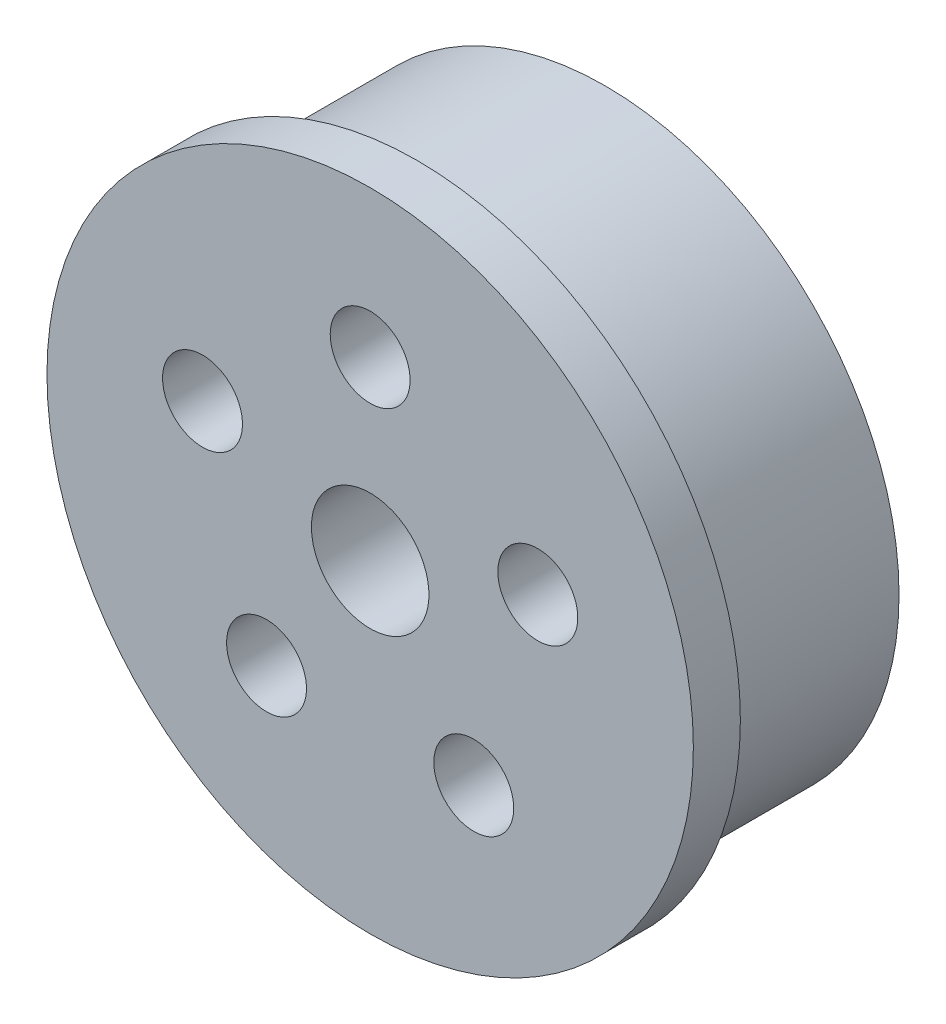
SolidWorks part; units mm, degrees
material "A2017"
ref_plane "正面" through (0, 0, 0) normal (0, 0, 1) x (1, 0, 0)
ref_plane "平面" through (0, 0, 0) normal (0, 1, 0) x (1, 0, 0)
ref_plane "右側面" through (0, 0, 0) normal (1, 0, 0) x (0, 0, -1)
sketch "ｽｹｯﾁ1" plane through (0, 0, 0) normal (0, 0, 1) x (1, 0, 0)
  circle A0 centre (0, 0) radius 12.5
  circle A1 centre (0, 7.5) radius 1.5
  circle A2 centre (0, 0) radius 7.5 construction
  circle A3 centre (7.1329, 2.3176) radius 1.5
  circle A4 centre (4.4084, -6.0676) radius 1.5
  circle A5 centre (-4.4084, -6.0676) radius 1.5
  circle A6 centre (-7.1329, 2.3176) radius 1.5
  point P16 (0, 0)
  dimension "D1" = 25
  dimension "D2" = 15
  dimension "D3" = 3
  dimension "D4" = 5
extrude "ﾎﾞｽ - 押し出し1" add sketch "ｽｹｯﾁ1" along normal blind 10
sketch "ｽｹｯﾁ3" plane through (0, 0, 10) normal (0, 0, 1) x (1, 0, 0)
  circle A0 centre (0, 0) radius 13.75
  circle A2 centre (0, 0) radius 12.5
  circle A3 centre (0, 0) radius 12.5
  dimension "D1" = 0
  dimension "D2" = 27.5
extrude "ﾎﾞｽ - 押し出し3" add sketch "ｽｹｯﾁ3" against normal blind 2
sketch "ｽｹｯﾁ4" plane through (0, 0, 0) normal (0, 0, -1) x (-1, 0, 0)
  circle A0 centre (0, 0) radius 2.5
  dimension "D1" = 5
extrude "ｶｯﾄ - 押し出し1" cut sketch "ｽｹｯﾁ4" against normal through all
hole_wizard "M3 穴付きねじ用座ぐり穴1" positions "ｽｹｯﾁ5" profile "ｽｹｯﾁ6" counterbore size "M3" standard "JIS" end condition through all
sketch "ｽｹｯﾁ5" plane through (0, 0, 0) normal (0, 0, -1) x (-1, 0, 0)
  point P0 (0, 7.5)
  point P3 (7.1329, 2.3176)
  point P6 (4.4084, -6.0676)
  point P9 (-4.4084, -6.0676)
  point P12 (-7.1329, 2.3176)
sketch "ｽｹｯﾁ6" plane through (0, 7.5, 0) normal (1, 0, 0) x (0, 1, 0)
  line L0 (0, 0) -> (0, 10)
  line L1 (0, 10) -> (1.7, 10)
  line L3 (1.7, 10) -> (1.7, 4)
  line L4 (1.7, 4) -> (3.5, 4)
  line L5 (3.5, 4) -> (3.5, 0)
  line L7 (3.5, 0) -> (0, 0)
  line L11 (0, -6.35) -> (0, 107.95) construction
  dimension "通し穴の直径" = 3.4
  dimension "通し穴の深さ" = 10
  dimension "座ぐり穴の直径" = 7
  dimension "座ぐり穴の深さ" = 4
